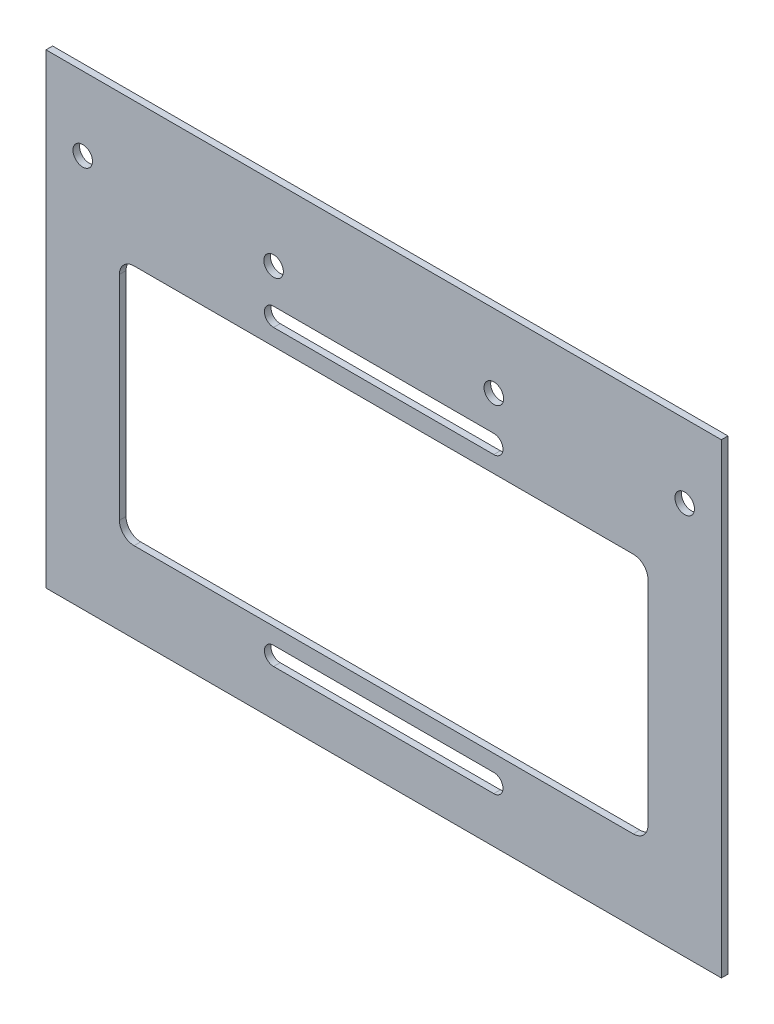
SolidWorks part; units mm, degrees
ref_plane "Front Plane" through (0, 0, 0) normal (0, 0, 1) x (1, 0, 0)
ref_plane "Top Plane" through (0, 0, 0) normal (0, 1, 0) x (1, 0, 0)
ref_plane "Right Plane" through (0, 0, 0) normal (1, 0, 0) x (0, 0, -1)
sketch "Sketch1" plane through (0, 0, 0) normal (0, 0, 1) x (1, 0, 0)
  line L1 (-116.84, 80.645) -> (116.84, 80.645)
  line L2 (-116.84, 80.645) -> (-116.84, -80.645)
  line L3 (-116.84, -80.645) -> (116.84, -80.645)
  line L4 (116.84, 80.645) -> (116.84, -80.645)
  line L5 (-116.84, 80.645) -> (116.84, -80.645) construction
  line L6 (-116.84, -80.645) -> (116.84, 80.645) construction
  line L7 (-86.36, 31.115) -> (86.36, 31.115)
  line L8 (-91.44, 26.035) -> (-91.44, -47.625)
  line L9 (-86.36, -52.705) -> (86.36, -52.705)
  line L10 (91.44, 26.035) -> (91.44, -47.625)
  line L11 (-91.44, 31.115) -> (91.44, -52.705) construction
  line L12 (-91.44, -52.705) -> (91.44, 31.115) construction
  arc A0 (86.36, -52.705) -> (91.44, -47.625) centre (86.36, -47.625) ccw
  arc A1 (86.36, 31.115) -> (91.44, 26.035) centre (86.36, 26.035) cw
  arc A2 (-91.44, 26.035) -> (-86.36, 31.115) centre (-86.36, 26.035) cw
  arc A3 (-86.36, -52.705) -> (-91.44, -47.625) centre (-86.36, -47.625) cw
  point P0 (0, 0)
  point P5 (0, -10.795)
  dimension "D7" = 5.08
  dimension "D1" = 25.4
  dimension "D2" = 161.29
  dimension "D3" = 182.88
  dimension "D4" = 83.82
  dimension "D5" = 27.94
  dimension "D6" = 233.68
extrude "Boss-Extrude1" add sketch "Sketch1" along normal blind 2.286
sketch "Sketch2" plane through (0, 0, 2.286) normal (0, 0, 1) x (1, 0, 0)
  line L0 (38.1, 40.005) -> (-38.1, 40.005) construction
  line L1 (38.1, 36.83) -> (-38.1, 36.83)
  line L2 (38.1, 43.18) -> (-38.1, 43.18)
  line L3 (-91.44, 26.035) -> (-91.44, -47.625) construction
  line L4 (-91.44, -10.795) -> (91.44, -10.795) construction
  line L5 (-91.44, 26.035) -> (-91.44, -47.625) construction
  line L6 (91.44, -47.625) -> (91.44, 26.035) construction
  line L7 (38.1, -61.595) -> (-38.1, -61.595) construction
  line L8 (38.1, -58.42) -> (-38.1, -58.42)
  line L9 (38.1, -64.77) -> (-38.1, -64.77)
  arc A0 (38.1, 36.83) -> (38.1, 43.18) centre (38.1, 40.005) ccw
  arc A1 (-38.1, 43.18) -> (-38.1, 36.83) centre (-38.1, 40.005) ccw
  arc A2 (38.1, -58.42) -> (38.1, -64.77) centre (38.1, -61.595) cw
  arc A3 (-38.1, -64.77) -> (-38.1, -58.42) centre (-38.1, -61.595) cw
  point P2 (0, 40.005)
  point P7 (-91.44, -10.795)
  point P19 (0, -61.595)
  dimension "D1" = 76.2
  dimension "D2" = 50.8
  dimension "D3" = 6.35
extrude "Cut-Extrude1" cut sketch "Sketch2" against normal through all
hole_wizard "1/4 Clearance Hole1" positions "Sketch4" profile "Sketch3" hole size "1/4" standard "ANSI Inch" end condition through all
sketch "Sketch4" plane through (0, 0, 2.286) normal (0, 0, 1) x (1, 0, 0)
  line L2 (116.84, 80.645) -> (-116.84, 80.645) construction
  line L3 (-38.1, 55.245) -> (38.1, 55.245) construction
  point P0 (-38.1, 55.245)
  point P8 (38.1, 55.245)
  point P22 (0, 55.245)
  dimension "D1" = 76.2
  dimension "D3" = 25.4
sketch "Sketch3" plane through (-38.1, 55.245, 2.286) normal (1, 0, 0) x (0, -1, 0)
  line L0 (0, 0) -> (0, 2.286)
  line L1 (0, 2.286) -> (3.3782, 2.286)
  line L2 (3.3782, 2.286) -> (3.3782, 0)
  line L5 (3.3782, 0) -> (0, 0)
  line L11 (0, -6.35) -> (0, 107.95) construction
  dimension "Thru Hole Dia." = 6.7564
  dimension "Thru Hole Depth" = 2.286
hole_wizard "1/4 Clearance Hole2" positions "Sketch8" profile "Sketch7" hole size "1/4" standard "ANSI Inch" end condition through all
sketch "Sketch8" plane through (0, 0, 2.286) normal (0, 0, 1) x (1, 0, 0)
  line L0 (-116.84, 80.645) -> (-116.84, -80.645) construction
  line L1 (116.84, -80.645) -> (116.84, 80.645) construction
  line L2 (116.84, 80.645) -> (-116.84, 80.645) construction
  point P0 (-104.14, 55.245)
  point P2 (104.14, 55.245)
  dimension "D1" = 12.7
  dimension "D2" = 12.7
  dimension "D3" = 25.4
sketch "Sketch7" plane through (-104.14, 55.245, 2.286) normal (1, 0, 0) x (0, -1, 0)
  line L0 (0, 0) -> (0, 2.286)
  line L1 (0, 2.286) -> (3.3782, 2.286)
  line L2 (3.3782, 2.286) -> (3.3782, 0)
  line L5 (3.3782, 0) -> (0, 0)
  line L11 (0, -6.35) -> (0, 107.95) construction
  dimension "Thru Hole Dia." = 6.7564
  dimension "Thru Hole Depth" = 2.286
